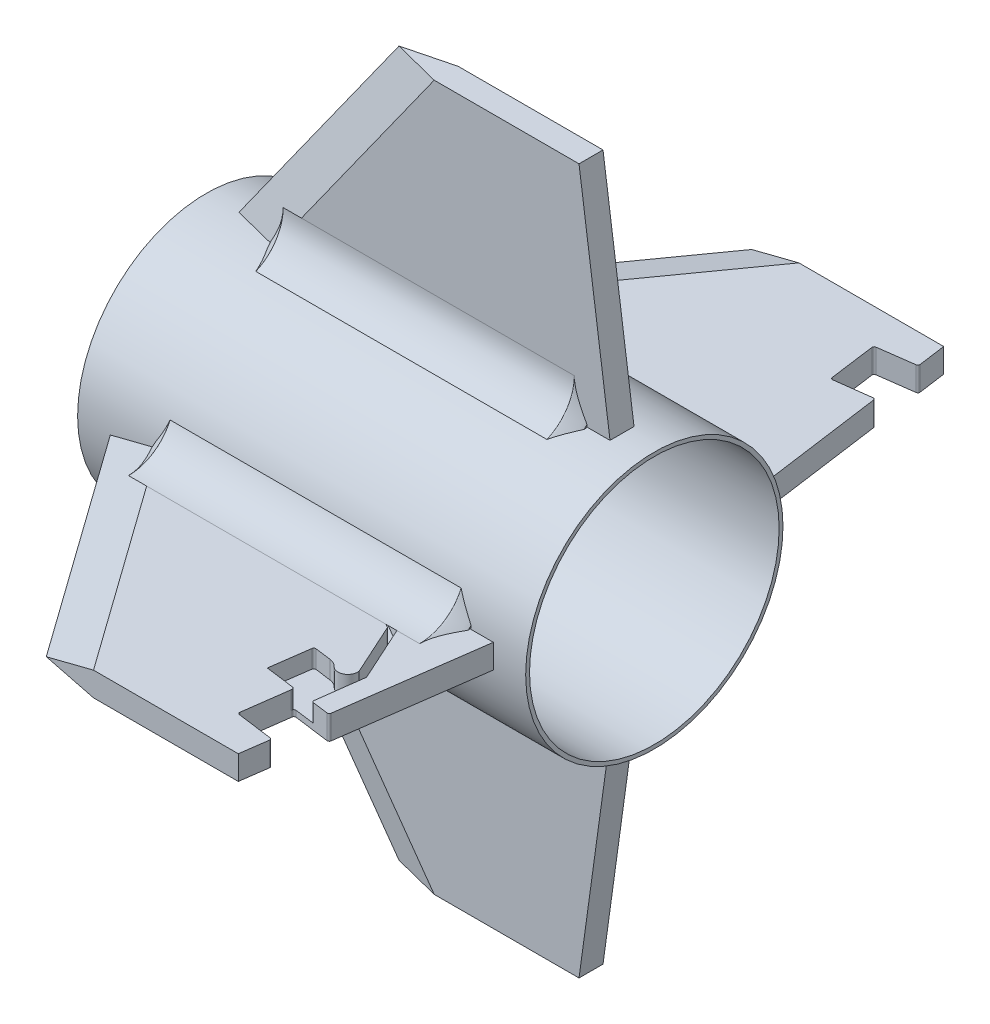
SolidWorks part; units mm, degrees
material "Wound G12 Fiberglass"
ref_plane "Front Plane" through (0, 0, 0) normal (0, 0, 1) x (1, 0, 0)
ref_plane "Top Plane" through (0, 0, 0) normal (0, 1, 0) x (1, 0, 0)
ref_plane "Right Plane" through (0, 0, 0) normal (1, 0, 0) x (0, 0, -1)
sketch "Sketch2" plane through (0, 0, 0) normal (0, 1, 0) x (1, 0, 0)
  line L16 (-44.199, 224.5036) -> (-44.199, 122.5036) construction
  line L32 (-44.199, 33.6036) -> (19.301, 33.6036) construction
  line L33 (-44.199, 122.5036) -> (-44.199, 33.6036) construction
  line L34 (95.501, 33.6036) -> (107.801, 122.5036)
  line L35 (-44.199, 122.5036) -> (19.301, 33.6036)
  line L36 (19.301, 33.6036) -> (95.501, 33.6036)
  line L37 (-44.199, 122.5036) -> (107.801, 122.5036)
extrude "Boss-Extrude1" add sketch "Sketch2" along normal blind 9.525
sketch "Sketch40" plane through (0, 0, -122.5036) normal (0, 0, -1) x (-1, 0, 0)
  line L1 (44.199, 9.525) -> (44.199, 0) construction
  line L3 (44.199, 4.7625) -> (25.4641, 0)
  line L7 (-107.801, 0) -> (44.199, 0) construction
  line L8 (44.199, 0) -> (25.4641, 0)
  line L11 (44.199, 0) -> (44.199, 4.7625)
extrude "Cut-Extrude11" cut sketch "Sketch40" along direction (0.5812, 0, 0.8137) on the side against the normal up to next (88.9 mm away)
sketch "Sketch41" plane through (0, 0, -122.5036) normal (0, 0, -1) x (-1, 0, 0)
  line L4 (44.199, 4.7625) -> (44.199, 9.525)
  line L5 (25.4641, 0) -> (25.4641, 9.525) construction
  line L6 (-107.801, 9.525) -> (44.199, 9.525) construction
  line L7 (25.4641, 9.525) -> (44.199, 9.525)
  line L8 (44.199, 4.7625) -> (25.4641, 9.525)
extrude "Cut-Extrude12" cut sketch "Sketch41" along direction (0.5812, 0, 0.8137) on the side against the normal up to next (88.9 mm away)
sketch "Sketch3" plane through (0, 9.525, 0) normal (0, 1, 0) x (1, 0, 0)
  line L19 (107.801, 122.5036) -> (107.801, 174.5036) construction
  line L20 (107.801, 174.5036) -> (-64.0208, 174.5036) construction
  line L21 (97.1137, 45.2595) -> (81.4578, 47.3779)
  line L22 (99.8638, 65.1363) -> (97.1137, 45.2595)
  line L23 (84.1395, 67.1973) -> (99.8638, 65.1363)
  line L24 (84.1395, 67.1973) -> (81.4578, 47.3779)
  line L25 (95.501, 33.6036) -> (107.801, 122.5036) construction
extrude "Cut-Extrude1" cut sketch "Sketch3" against normal through all
fillet "Fillet25" radius 0.7937 4 edges at (99.8638, 4.7625, -65.1363) (97.1137, 4.7625, -45.2595) (81.4578, 4.7625, -47.3779) (84.1395, 4.7625, -67.1973)
sketch "Sketch4" plane through (0, 9.525, 0) normal (0, 1, 0) x (1, 0, 0)
  line L51 (-44.199, 173.5036) -> (145.6689, 173.5036) construction
  line L107 (93.956, 80.0077) -> (94.6266, 85.1293)
  line L115 (74.0468, 85.2066) -> (81.3247, 84.2473)
  line L123 (93.956, 80.0077) -> (92.1413, 66.1485)
  line L124 (92.1413, 66.1485) -> (89.173, 66.5376)
  line L125 (89.173, 66.5376) -> (88.8129, 63.7802)
  line L126 (88.8129, 63.7802) -> (84.8834, 64.2934)
  line L131 (71.7832, 68.8168) -> (73.1874, 78.9838)
  line L137 (73.1874, 78.9838) -> (74.0468, 85.2066)
  line L138 (94.5617, 85.564) -> (84.1666, 108.4293)
  line L139 (83.8424, 108.7887) -> (60.4974, 122.4493)
  line L140 (107.801, 122.5036) -> (-25.4641, 122.5036) construction
  line L142 (91.0571, 86.024) -> (81.8297, 106.3209)
  line L143 (81.5054, 106.6803) -> (58.8894, 119.9143)
  line L144 (58.8894, 119.9143) -> (54.4645, 122.5036)
  line L147 (90.9814, 80.3972) -> (91.5703, 84.8951) construction
  line L148 (91.5703, 84.8951) -> (81.7246, 106.5521) construction
  line L149 (93.956, 80.0077) -> (94.6563, 85.3559) construction
  line L150 (94.6563, 85.3559) -> (84.0615, 108.6604) construction
  line L151 (81.7246, 106.5521) -> (58.8894, 119.9143) construction
  line L152 (84.0615, 108.6604) -> (60.4045, 122.5036) construction
  line L155 (54.4645, 122.5036) -> (60.2969, 122.5036)
  line L174 (84.4986, -92.3477) -> (84.7467, -92.3782)
  line L175 (64.7164, -87.2993) -> (72.0026, -88.1939)
  line L176 (84.7467, -92.3782) -> (83.0405, -106.2738)
  line L177 (83.0405, -106.2738) -> (80.0629, -105.9082)
  line L178 (80.0629, -105.9082) -> (79.7268, -108.6455)
  line L179 (79.7268, -108.6455) -> (75.7496, -108.1572)
  line L180 (75.7496, -108.1572) -> (76.0857, -105.4199)
  line L181 (76.0857, -105.4199) -> (62.6933, -103.7756)
  line L182 (62.6933, -103.7756) -> (64.7164, -87.2993)
  line L183 (84.4986, -92.3477) -> (78.6579, -91.6306)
  line L185 (99.0824, 65.2387) -> (84.9233, 67.0946) construction
  line L186 (83.9824, 66.0359) -> (84.1347, 67.1979)
  line L187 (84.0336, 66.414) -> (81.5642, 48.1645) construction
  line L188 (83.9824, 66.0359) -> (85.092, 65.891)
  line L189 (84.8834, 64.2934) -> (85.092, 65.891)
  line L190 (71.7832, 68.8168) -> (84.1347, 67.1979)
  arc A0 (81.3247, 84.2473) -> (84.1061, 82.9729) centre (80.6452, 79.0919) cw
  arc A1 (85.1679, 82.026) -> (84.1061, 82.9729) centre (54.93, 49.1861) ccw
  arc A8 (94.6266, 85.1293) -> (94.5617, 85.564) centre (93.8339, 85.2331) ccw
  arc A9 (81.8297, 106.3209) -> (81.5054, 106.6803) centre (81.1014, 105.9898) ccw
  arc A10 (84.1666, 108.4293) -> (83.8424, 108.7887) centre (83.4383, 108.0982) ccw
  arc A11 (60.4974, 122.4493) -> (60.2969, 122.5036) centre (60.2969, 122.1067) ccw
  arc A18 (85.1679, 82.026) -> (91.0571, 86.024) centre (87.2104, 85.3538) ccw
  arc A23 (72.0026, -88.1939) -> (74.7951, -89.4435) centre (71.3689, -93.3551) cw
  arc A24 (75.8654, -90.381) -> (74.7951, -89.4435) centre (45.9204, -123.4882) ccw
  arc A25 (78.6579, -91.6306) -> (75.8654, -90.381) centre (79.2916, -86.4693) cw
  dimension "D5" = 0.8
  dimension "D6" = 0.8
  dimension "D7" = 0.3969
extrude "Cut-Extrude8" cut sketch "Sketch4" against normal blind 7.112
fillet "Fillet31" radius 0.7937 4 edges at (54.4645, 5.969, -122.5036) (92.1413, 5.969, -66.1485) (74.0468, 5.969, -85.2066) (84.1347, 5.969, -67.1979)
sketch "Sketch20" plane through (0, 0, 0) normal (1, 0, 0) x (0, 0, -1)
  line L0 (122.5036, 4.7625) -> (173.5576, 4.7625) construction
  circle A4 centre (173.5576, 4.7625) radius 51.054
  dimension "D1" = 102.108
extrude "Boss-Extrude7" add sketch "Sketch20" along normal blind 120.626 and the other way blind 57.174
pattern_circular "CirPattern6" count 2 over 360 about axis through (0, 4.7625, -173.5576) along (1, 0, 0) of bodies 243 213
ref_plane "Plane3" through (0, 0, -173.5576) normal (0, 0, -1) x (-1, 0, 0)
sketch "Sketch34" plane through (0, 0, -173.5576) normal (0, 0, -1) x (-1, 0, 0)
  line L8 (-107.801, 9.525) -> (-107.801, 55.8165) construction
  line L9 (57.174, 55.8165) -> (-120.626, 55.8165) construction
sketch "Sketch35" plane through (0, 0, -173.5576) normal (0, 0, -1) x (-1, 0, 0)
  line L15 (44.199, -46.2375) -> (44.199, -135.1375) construction
  line L16 (44.199, -135.1375) -> (-19.301, -135.1375) construction
  line L17 (44.199, 144.6625) -> (-19.301, 144.6625) construction
  line L18 (44.199, 55.7625) -> (44.199, 144.6625) construction
  line L19 (44.199, 4.7625) -> (-254.4767, 4.7625) construction
  line L20 (44.199, 55.7625) -> (44.199, -46.2375) construction
  line L21 (44.199, -46.2375) -> (-107.801, -46.2375)
  line L22 (-19.301, -135.1375) -> (-95.501, -135.1375)
  line L23 (44.199, -46.2375) -> (-19.301, -135.1375)
  line L24 (-95.501, -135.1375) -> (-107.801, -46.2375)
  line L25 (-95.501, 144.6625) -> (-107.801, 55.7625)
  line L26 (44.199, 55.7625) -> (-19.301, 144.6625)
  line L27 (-19.301, 144.6625) -> (-95.501, 144.6625)
  line L28 (44.199, 55.7625) -> (-107.801, 55.7625)
extrude "Boss-Extrude11" add sketch "Sketch35" along normal blind 4.7625 and the other way blind 4.7625 separate body
sketch "Sketch42" plane through (0, -135.1375, 0) normal (0, -1, 0) x (1, 0, 0)
  line L0 (19.301, -173.5576) -> (31.5389, -168.7951)
  line L1 (19.301, -168.7951) -> (19.301, -178.3201) construction
  line L2 (95.501, -168.7951) -> (19.301, -168.7951) construction
  line L3 (31.5389, -168.7951) -> (31.5389, -178.3201)
  line L4 (95.501, -178.3201) -> (19.301, -178.3201) construction
  line L5 (31.5389, -178.3201) -> (19.301, -173.5576)
  line L6 (19.301, -178.3201) -> (31.5389, -178.3201)
  line L7 (19.301, -173.5576) -> (19.301, -168.7951)
  line L8 (19.301, -168.7951) -> (31.5389, -168.7951)
  line L9 (19.301, -168.7951) -> (31.5389, -168.7951)
  line L10 (31.5389, -178.3201) -> (19.301, -178.3201)
  line L11 (19.301, -173.5576) -> (19.301, -178.3201)
sketch "Sketch43" plane through (0, -46.2375, 0) normal (0, 1, 0) x (1, 0, 0)
  line L6 (-44.199, 173.5576) -> (-44.199, 178.3201)
  line L7 (-44.199, 168.7951) -> (-44.199, 178.3201) construction
  line L10 (-44.199, 178.3201) -> (-25.4641, 178.3201)
  line L11 (-44.199, 178.3201) -> (19.301, 178.3201) construction
  line L12 (-25.4641, 178.3201) -> (-25.4641, 168.7951)
  line L13 (-44.199, 168.7951) -> (19.301, 168.7951) construction
  line L14 (-25.4641, 168.7951) -> (-44.199, 168.7951)
  line L15 (-44.199, 168.7951) -> (-44.199, 173.5576)
  line L16 (-44.199, 173.5576) -> (-25.4641, 178.3201)
  line L17 (-44.199, 173.5576) -> (-25.4641, 168.7951)
extrude "Cut-Extrude14" cut sketch "Sketch43" along direction (-0.5812, 0.8137, 0) on the side against the normal up to next (88.9 mm away)
sketch "Sketch44" plane through (0, 55.7625, 0) normal (0, -1, 0) x (1, 0, 0)
  line L0 (-44.199, -173.5576) -> (-44.199, -168.7951)
  line L1 (-44.199, -168.7951) -> (-44.199, -178.3201) construction
  line L2 (-44.199, -168.7951) -> (-25.4641, -168.7951)
  line L3 (-25.4641, -168.7951) -> (-44.199, -173.5576)
  line L4 (-44.199, -173.5576) -> (-25.4641, -178.3201)
  line L5 (107.801, -178.3201) -> (-44.199, -178.3201) construction
  line L6 (-25.4641, -178.3201) -> (-44.199, -178.3201)
  line L7 (-44.199, -178.3201) -> (-44.199, -173.5576)
  line M1 (-44.199, -168.7951) -> (-44.199, -178.3201)
  line M2 (-44.199, -178.3201) -> (107.801, -178.3201)
  line M4 (107.801, -168.7951) -> (-44.199, -168.7951)
extrude "Cut-Extrude15" cut sketch "Sketch44" along direction (0.5812, 0.8137, 0) on the side against the normal up to next (88.9 mm away) contours L3 M4 M1 | L4 M1 M2
sketch "Sketch24" plane through (120.626, 0, 0) normal (1, 0, 0) x (0, 0, -1)
  line L2 (173.5576, -5.2388) -> (173.5576, 5.2388) construction
  circle A3 centre (173.5576, 4.7625) radius 49.53
  dimension "D1" = 99.06
extrude "Cut-Extrude16" cut sketch "Sketch24" against normal up to next (177.8 mm away)
sketch "Sketch47" plane through (120.626, 0, 0) normal (1, 0, 0) x (0, 0, -1)
  line L1 (178.3201, 144.6625) -> (178.3201, 55.7625) construction
  line L2 (178.3201, 55.5939) -> (189.1923, 54.4267)
  line L3 (173.5576, 52.8298) -> (173.5576, -44.7675) construction
  line L5 (168.7951, 55.5939) -> (157.9229, 54.4267)
  line L12 (178.3201, 55.5939) -> (178.3201, 70.9214)
  line L14 (168.7951, 55.5939) -> (168.7951, 70.9214)
  circle A0 centre (196.2685, 70.9214) radius 17.9484 construction
  circle A1 centre (173.5576, 4.7625) radius 51.054 construction
  arc A2 (178.3201, 70.9214) -> (189.1923, 54.4267) centre (196.2685, 70.9214) ccw
  circle A3 centre (173.5576, 4.7625) radius 49.53 construction
  circle A4 centre (150.8467, 70.9214) radius 17.9484 construction
  arc A5 (168.7951, 70.9214) -> (157.9229, 54.4267) centre (150.8467, 70.9214) cw
  point P58 (174.5036, 4.7625)
extrude "Boss-Extrude13" add sketch "Sketch47" against normal blind 122.5 and the other way blind 3 from offset 25 separate body offset against normal yes
fillet "Fillet17" radius 5 2 edges at (98.626, 61.0436, -181.2827) (-26.874, 61.0436, -181.2827)
fillet "Fillet18" radius 5 2 edges at (-26.874, 61.0436, -165.8326) (98.626, 61.0436, -165.8326)
pattern_circular "CirPattern9" count 4 over 360 about axis through (120.626, 4.7625, -173.5576) along (1, 0, 0) of bodies 225 231
